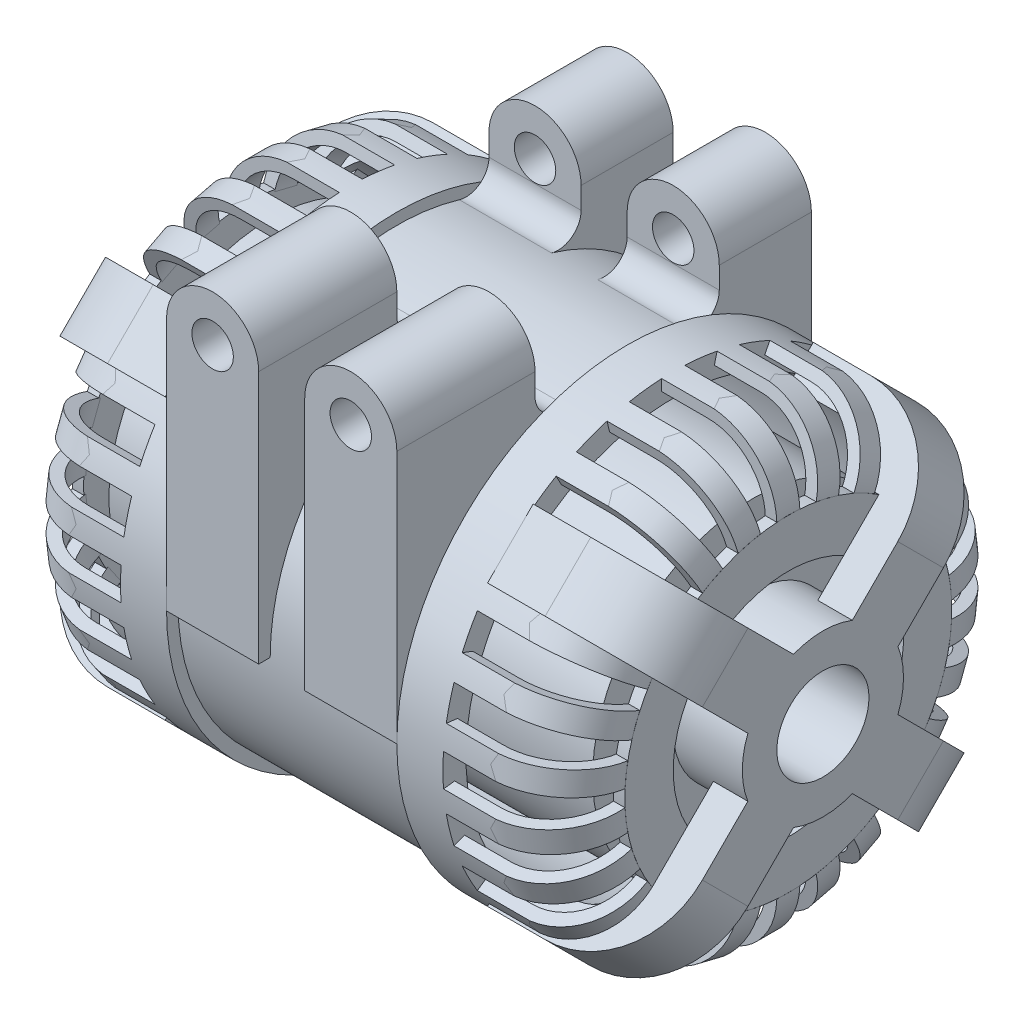
SolidWorks part; units mm, degrees
material "Plain Carbon Steel"
ref_plane "Front Plane" through (0, 0, 0) normal (0, 0, 1) x (1, 0, 0)
ref_plane "Top Plane" through (0, 0, 0) normal (0, 1, 0) x (1, 0, 0)
ref_plane "Right Plane" through (0, 0, 0) normal (1, 0, 0) x (0, 0, -1)
sketch "Sketch1" plane through (0, 0, 0) normal (1, 0, 0) x (0, 0, -1)
  circle A0 centre (0, 0) radius 50
  circle A1 centre (0, 0) radius 47.5
  dimension "D1" = 100
  dimension "D2" = 95
extrude "Boss-Extrude1" add sketch "Sketch1" against normal blind 10
ref_axis "Axis1" through (-2, 0, 0) along (1, 0, 0)
sketch "Sketch5" plane through (0, 0, 0) normal (0, 0, 1) x (1, 0, 0)
  line L0 (0, 50) -> (10, 50)
  line L2 (0, 50) -> (0, 47.5)
  line L4 (0, 47.5) -> (10, 47.5)
  line L5 (22.5, 35) -> (25, 35)
  arc A0 (10, 50) -> (25, 35) centre (10, 35) cw
  arc A1 (10, 47.5) -> (22.5, 35) centre (10, 35) cw
  dimension "D1" = 2.5
  dimension "D2" = 50
  dimension "D3" = 10
  dimension "D4" = 15
extrude "Boss-Extrude2" add sketch "Sketch5" along normal blind 2.5 and the other way blind 2.5
pattern_circular "CirPattern1" count 26 over 360 about axis through (-2, 0, 0) along (1, 0, 0) of "Boss-Extrude2"
ref_plane "Plane1" through (25, 0, 0) normal (-1, 0, 0) x (0, 0, 1)
sketch "Sketch6" plane through (25, 0, 0) normal (-1, 0, 0) x (0, 0, 1)
  circle A0 centre (0, 0) radius 35.5
  circle A1 centre (0, 0) radius 25
  dimension "D1" = 71
  dimension "D2" = 50
extrude "Boss-Extrude3" add sketch "Sketch6" along normal blind 2.5
sketch "Sketch7" plane through (0, 0, 0) normal (1, 0, 0) x (0, 0, -1)
  circle A0 centre (0, 0) radius 50
  dimension "D1" = 100
extrude "Cut-Extrude4" cut sketch "Sketch7" along normal through all flip side to cut
ref_plane "Plane2" through (0, 0, 0) normal (0, -0.7071, 0.7071) x (1, 0, 0)
sketch "Sketch8" plane through (0, 0, 0) normal (0, -0.7071, 0.7071) x (1, 0, 0)
  line L0 (0, 42.5) -> (0, 50)
  line L2 (0, 50) -> (12.5, 50)
  line L3 (32.5, 30) -> (32.5, -10)
  line L4 (0, 42.5) -> (12.5, 42.5)
  line L6 (25, 30) -> (25, -10)
  line L7 (25, -10) -> (32.5, -10)
  arc A0 (12.5, 50) -> (32.5, 30) centre (12.5, 30) cw
  arc A1 (12.5, 42.5) -> (25, 30) centre (12.5, 30) cw
  dimension "D2" = 20
  dimension "D1" = 12.5
  dimension "D3" = 50
  dimension "D4" = 40
  dimension "D5" = 7.5
extrude "Boss-Extrude4" add sketch "Sketch8" along normal blind 7 and the other way blind 7
pattern_circular "CirPattern2" count 4 over 360 about axis through (-2, 0, 0) along (1, 0, 0) of "Boss-Extrude4"
sketch "Sketch9" plane through (32.5, 0, 0) normal (1, 0, 0) x (0, 0, -1)
  circle A0 centre (0, 0) radius 17.5
  dimension "D1" = 35
extrude "Boss-Extrude5" add sketch "Sketch9" against normal blind 15
ref_plane "Plane3" through (-35, 0, 0) normal (1, 0, 0) x (0, 0, -1)
mirror "Mirror2" about plane through (-35, 0, 0) normal (1, 0, 0) of bodies 111
sketch "Sketch10" plane through (17.5, 0, 0) normal (-1, 0, 0) x (0, 0, 1)
  circle A0 centre (0, 0) radius 35
  dimension "D1" = 70
extrude "Boss-Extrude6" add sketch "Sketch10" along normal up to surface (105 mm away) up to face at (-87.5, 17.5, 0)
sketch "Sketch11" plane through (-35, 0, 0) normal (1, 0, 0) x (0, 0, -1)
  circle A0 centre (0, 0) radius 47.5
  circle A1 centre (0, 0) radius 45
  dimension "D1" = 95
  dimension "D2" = 90
extrude "Boss-Extrude7" add sketch "Sketch11" along normal blind 35 and the other way blind 35
ref_plane "Plane4" through (0, 65, 0) normal (0, 1, 0) x (1, 0, 0)
sketch "Sketch13" plane through (0, 65, 0) normal (0, 1, 0) x (1, 0, 0)
  line L0 (0, 50) -> (0, -50) construction
  line L1 (-60, 20) -> (-40, 20)
  line L2 (-60, 20) -> (-60, 40)
  line L3 (-60, 40) -> (-40, 40)
  line L4 (-40, 20) -> (-40, 40)
  line L5 (-30, 20) -> (-10, 20)
  line L6 (-30, 20) -> (-30, 40)
  line L7 (-30, 40) -> (-10, 40)
  line L8 (-10, 20) -> (-10, 40)
  line L9 (-60, -40) -> (-40, -40)
  line L10 (-60, -40) -> (-60, -20)
  line L11 (-60, -20) -> (-40, -20)
  line L12 (-40, -40) -> (-40, -20)
  line L13 (-30, -40) -> (-10, -40)
  line L14 (-30, -40) -> (-30, -20)
  line L15 (-30, -20) -> (-10, -20)
  line L16 (-10, -40) -> (-10, -20)
  line L17 (-70, -50) -> (-70, 50) construction
  dimension "D1" = 10
  dimension "D2" = 10
  dimension "D3" = 20
  dimension "D4" = 40
  dimension "D5" = 40
extrude "Boss-Extrude8" add sketch "Sketch13" against normal up to surface (21.9158 mm away) up to face at (-60, 0, -47.5)
sketch "Sketch14" plane through (0, 0, 0) normal (0, 0, 1) x (1, 0, 0)
  line L0 (-60, 30) -> (-60, 65) construction
  line L1 (-60, 65) -> (-40, 65) construction
  line L2 (-30, 25.6174) -> (-30, 65) construction
  line L3 (-40, 55) -> (-30, 55)
  line L4 (-60, 55) -> (-77.0029, 55)
  line L5 (-77.0029, 55) -> (-77.0029, 106.4379)
  line L6 (-77.0029, 106.4379) -> (0, 106.4379)
  line L7 (0, 106.4379) -> (0, 55)
  line L8 (0, 55) -> (-10, 55)
  circle A0 centre (-50, 55) radius 4.5
  circle A1 centre (-20, 55) radius 4.5
  arc A2 (-40, 55) -> (-60, 55) centre (-50, 55) ccw
  arc A3 (-10, 55) -> (-30, 55) centre (-20, 55) ccw
  dimension "D3" = 20
  dimension "D4" = 9
  dimension "D1" = 10
  dimension "D2" = 10
  dimension "D5" = 10
extrude "Cut-Extrude5" cut sketch "Sketch14" against normal through all both and the other way through all
fillet "Fillet1" radius 5 6 edges at (-50, 25.6174, -40) (-20, 25.6174, -40) (-20, 43.0842, -20) (-50, 43.0842, -20) (-50, 43.0842, 20) (-20, 43.0842, 20)
ref_plane "Plane5" through (0, 0, 50) normal (0, 0, 1) x (1, 0, 0)
sketch "Sketch15" plane through (0, 0, 50) normal (0, 0, 1) x (1, 0, 0)
  line L0 (-60, 55) -> (-60, 0)
  line L1 (-60, 0) -> (-40, 0)
  line L2 (-40, 0) -> (-40, 55)
  line L3 (-30, 55) -> (-30, 0)
  line L4 (-30, 0) -> (-10, 0)
  line L5 (-10, 0) -> (-10, 55)
  line L6 (-60, 41.3068) -> (-40, 41.3068)
  line L7 (-30, 41.3068) -> (-10, 41.3068)
  arc A0 (-60, 55) -> (-40, 55) centre (-50, 55) cw
  circle A1 centre (-50, 55) radius 4.5
  arc A2 (-30, 55) -> (-10, 55) centre (-20, 55) cw
  circle A3 centre (-20, 55) radius 4.5
  point P23 (0, 0)
  point P24 (0, 0)
  point P25 (0, 0)
  dimension "D1" = 9
extrude "Boss-Extrude10" add sketch "Sketch15" against normal up to surface (2.5 mm away) contours L6 L0 L1 L2 | L7 L3 L4 L5 region at (-50, 20.6534, 50) region at (-20, 20.6534, 50) up to face at (-20, 27.0756, -0.0719)
extrude "Boss-Extrude11" add sketch "Sketch15<3>" against normal up to surface (10 mm away) contours A0 L0 L6 L2 A1 | A2 L3 L7 L5 A3 region at (-50, 64.6899, 50) region at (-20, 64.6899, 50) up to face at (-15.5, 55, 40)
sketch "Sketch15<3>" plane through (0, 0, 50) normal (0, 0, 1) x (1, 0, 0) same geometry as "Sketch15"
sketch "Sketch18" plane through (32.5, 0, 0) normal (1, 0, 0) x (0, 0, -1)
  circle A0 centre (0, 0) radius 10
  dimension "D1" = 20
extrude "Cut-Extrude6" cut sketch "Sketch18" against normal blind 20
